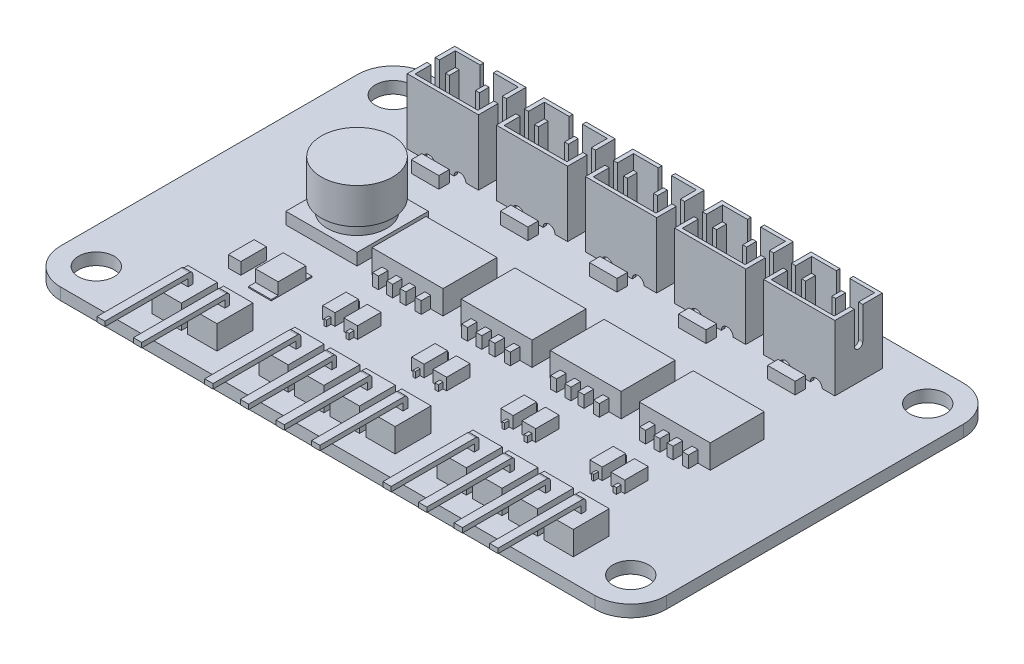
SolidWorks part; units mm, degrees
ref_plane "前视基准面" through (0, 0, 0) normal (0, 0, 1) x (1, 0, 0)
ref_plane "上视基准面" through (0, 0, 0) normal (0, 1, 0) x (1, 0, 0)
ref_plane "右视基准面" through (0, 0, 0) normal (1, 0, 0) x (0, 0, -1)
sketch "草图1" plane through (0, 0, 0) normal (0, 1, 0) x (1, 0, 0)
  line L1 (-22.5, 15.5) -> (22.5, 15.5)
  line L2 (-25.5, 12.5) -> (-25.5, -12.5)
  line L3 (-22.5, -15.5) -> (22.5, -15.5)
  line L4 (25.5, 12.5) -> (25.5, -12.5)
  line L5 (-25.5, 15.5) -> (25.5, -15.5) construction
  line L6 (-25.5, -15.5) -> (25.5, 15.5) construction
  arc A0 (22.5, 15.5) -> (25.5, 12.5) centre (22.5, 12.5) cw
  arc A1 (22.5, -15.5) -> (25.5, -12.5) centre (22.5, -12.5) ccw
  arc A2 (-25.5, -12.5) -> (-22.5, -15.5) centre (-22.5, -12.5) ccw
  arc A3 (-22.5, 15.5) -> (-25.5, 12.5) centre (-22.5, 12.5) ccw
  point P0 (0, 0)
  dimension "D3" = 3
  dimension "D1" = 51
  dimension "D2" = 31
extrude "凸台-拉伸1" add sketch "草图1" along normal blind 1
sketch "草图2" plane through (0, 1, 0) normal (0, 1, 0) x (1, 0, 0)
  line L1 (-22.5, 12.5) -> (22.5, 12.5)
  line L2 (-22.5, 12.5) -> (-22.5, -12.5)
  line L3 (-22.5, -12.5) -> (22.5, -12.5)
  line L4 (22.5, 12.5) -> (22.5, -12.5)
  line L5 (-22.5, 12.5) -> (22.5, -12.5) construction
  line L6 (-22.5, -12.5) -> (22.5, 12.5) construction
  circle A0 centre (-22.5, 12.5) radius 1.5
  point P0 (0, 0)
  dimension "D3" = 3
  dimension "D1" = 45
  dimension "D2" = 25
extrude "切除-拉伸1" cut sketch "草图2" against normal blind 1.5 contours L2 A0 L1 | L1 A0 L2 region at (-22.7122, 1, -12.7122) region at (-21.8634, 1, -11.8634)
mirror "镜向1" about plane through (0, 0, 0) normal (0, 0, 1) of "切除-拉伸1"
mirror "镜向2" about plane through (0, 0, 0) normal (1, 0, 0) of "镜向1"
sketch "草图3" plane through (0, 1, 0) normal (0, 1, 0) x (1, 0, 0)
  line L1 (-17.9678, 13.1472) -> (-11.9678, 13.1472)
  line L2 (-17.9678, 13.1472) -> (-17.9678, 9.1472)
  line L3 (-17.9678, 9.1472) -> (-11.9678, 9.1472)
  line L4 (-11.9678, 13.1472) -> (-11.9678, 9.1472)
  line L5 (-17.9678, 13.1472) -> (-11.9678, 9.1472) construction
  line L6 (-17.9678, 9.1472) -> (-11.9678, 13.1472) construction
  point P4 (-14.9678, 11.1472)
  dimension "D1" = 6
  dimension "D2" = 4
extrude "凸台-拉伸2" add sketch "草图3" along normal blind 5.5
sketch "草图4" plane through (0, 6.5, 0) normal (0, 1, 0) x (1, 0, 0)
  line L1 (-17.6136, 12.8433) -> (-12.3219, 12.8433)
  line L2 (-17.6136, 12.8433) -> (-17.6136, 9.4512)
  line L3 (-17.6136, 9.4512) -> (-12.3219, 9.4512)
  line L4 (-12.3219, 12.8433) -> (-12.3219, 9.4512)
  line L5 (-17.6136, 12.8433) -> (-12.3219, 9.4512) construction
  line L6 (-17.6136, 9.4512) -> (-12.3219, 12.8433) construction
  point P0 (-14.9678, 11.1472)
extrude "切除-拉伸2" cut sketch "草图4" against normal blind 5.5
sketch "草图5" plane through (0, 1, 0) normal (0, 1, 0) x (1, 0, 0)
  line L0 (-14.9678, 12.8433) -> (-14.9678, 9.4512) construction
  line L1 (-12.3219, 12.8433) -> (-17.6136, 12.8433) construction
  line L2 (-17.6136, 9.4512) -> (-12.3219, 9.4512) construction
  line L3 (-13.5358, 10.7921) -> (-13.867, 10.7921)
  line L4 (-16.3997, 11.6123) -> (-16.0685, 11.6123)
  line L5 (-16.3997, 11.6123) -> (-16.3997, 10.7921)
  line L6 (-16.3997, 10.7921) -> (-16.0685, 10.7921)
  line L7 (-16.0685, 11.6123) -> (-16.0685, 10.7921)
  line L8 (-16.3997, 11.6123) -> (-16.0685, 10.7921) construction
  line L9 (-16.3997, 10.7921) -> (-16.0685, 11.6123) construction
  line L10 (-13.867, 11.6123) -> (-13.867, 10.7921)
  line L11 (-13.5358, 11.6123) -> (-13.5358, 10.7921)
  line L12 (-13.5358, 11.6123) -> (-13.867, 11.6123)
  point P10 (-16.2341, 11.2022)
extrude "凸台-拉伸3" add sketch "草图5" along normal blind 5.5
sketch "草图6" plane through (0, 0, -12.8433) normal (0, 0, 1) x (1, 0, 0)
  line L0 (-14.9678, 9.3795) -> (-14.9678, 3.6205) construction
  line L1 (-11.9678, 6.5) -> (-17.9678, 6.5) construction
  line L2 (-14.4041, 9.3795) -> (-14.4041, 3.6205)
  line L3 (-15.5314, 9.3795) -> (-15.5314, 3.6205)
  line L4 (-14.4041, 6.5) -> (-15.5314, 6.5)
  arc A0 (-14.4041, 9.3795) -> (-15.5314, 9.3795) centre (-14.9678, 9.3795) ccw
  arc A1 (-15.5314, 3.6205) -> (-14.4041, 3.6205) centre (-14.9678, 3.6205) ccw
  point P4 (-14.9678, 6.5)
  line M5 (-12.3219, 6.5) -> (-17.6136, 6.5)
extrude "切除-拉伸6" cut sketch "草图6" against normal blind 1 contours L3 A1 L2 L4 M5 region at (-14.9678, 4.8365, -12.8433)
sketch "草图7" plane through (-11.9678, 0, 0) normal (1, 0, 0) x (0, 0, -1)
  line L0 (11.1472, 9.2199) -> (11.1472, 3.7801) construction
  line L1 (9.1472, 6.5) -> (13.1472, 6.5) construction
  line L2 (11.5011, 9.2199) -> (11.5011, 3.7801)
  line L3 (10.7934, 9.2199) -> (10.7934, 3.7801)
  arc A0 (11.5011, 9.2199) -> (10.7934, 9.2199) centre (11.1472, 9.2199) ccw
  arc A1 (10.7934, 3.7801) -> (11.5011, 3.7801) centre (11.1472, 3.7801) ccw
  point P4 (11.1472, 6.5)
extrude "切除-拉伸7" cut sketch "草图7" against normal blind 1
sketch "草图8" plane through (-17.6136, 0, 0) normal (1, 0, 0) x (0, 0, -1)
  line L0 (11.5011, 3.7801) -> (11.5011, 6.5) construction
  line L1 (10.7934, 6.5) -> (10.7934, 3.7801) construction
  line L2 (11.5011, 3.7801) -> (11.5011, 6.5)
  line L3 (10.7934, 6.5) -> (10.7934, 3.7801)
  line L4 (11.5011, 6.5) -> (10.7934, 6.5)
  arc A0 (10.7934, 3.7801) -> (11.5011, 3.7801) centre (11.1472, 3.7801) ccw construction
  arc A1 (10.7934, 3.7801) -> (11.5011, 3.7801) centre (11.1472, 3.7801) ccw
extrude "切除-拉伸8" cut sketch "草图8" against normal blind 1
pattern_linear "阵列(线性)1" count 5 spacing 7.5 along (1, 0, 0) of "凸台-拉伸2"
pattern_linear "阵列(线性)2" count 5 spacing 7.5 along (1, 0, 0) of "切除-拉伸2"
pattern_linear "阵列(线性)3" count 5 spacing 7.5 along (1, 0, 0) of "凸台-拉伸3"
pattern_linear "阵列(线性)4" count 5 spacing 7.5 along (1, 0, 0) of "切除-拉伸7"
pattern_linear "阵列(线性)5" count 5 spacing 7.5 along (1, 0, 0) of "切除-拉伸6"
pattern_linear "阵列(线性)6" count 5 spacing 7.5 along (1, 0, 0) of "切除-拉伸8"
sketch "草图9" plane through (0, 1, 0) normal (0, 1, 0) x (1, 0, 0)
  line L1 (-17.5454, 4.5054) -> (-11.5454, 4.5054)
  line L2 (-17.5454, 4.5054) -> (-17.5454, -1.4946)
  line L3 (-17.5454, -1.4946) -> (-11.5454, -1.4946)
  line L4 (-11.5454, 4.5054) -> (-11.5454, -1.4946)
  line L5 (-17.5454, 4.5054) -> (-11.5454, -1.4946) construction
  line L6 (-17.5454, -1.4946) -> (-11.5454, 4.5054) construction
  point P4 (-14.5454, 1.5054)
  dimension "D1" = 6
  dimension "D2" = 6
extrude "凸台-拉伸4" add sketch "草图9" along normal blind 1
sketch "草图11" plane through (0, 2, 0) normal (0, 1, 0) x (1, 0, 0)
  circle A0 centre (-14.5424, 1.4949) radius 2.5
  point P2 (-14.2861, 1.5685)
  point P3 (0, 0)
  point P4 (0, 0)
  point P5 (0, 0)
  point P6 (0, 0)
  point P7 (-14.5424, 1.4949)
  dimension "D1" = 5
extrude "凸台-拉伸5" add sketch "草图11" along normal blind 1
sketch "草图12" plane through (0, 3, 0) normal (0, 1, 0) x (1, 0, 0)
  circle A0 centre (-14.5424, 1.4949) radius 3
  dimension "D1" = 6
extrude "凸台-拉伸6" add sketch "草图12" along normal blind 3
sketch "草图13" plane through (0, 1, 0) normal (0, 1, 0) x (1, 0, 0)
  line L1 (-16.0248, 8.431) -> (-13.7085, 8.431)
  line L2 (-16.0248, 8.431) -> (-16.0248, 7.5461)
  line L3 (-16.0248, 7.5461) -> (-13.7085, 7.5461)
  line L4 (-13.7085, 8.431) -> (-13.7085, 7.5461)
  line L5 (-16.0248, 8.431) -> (-13.7085, 7.5461) construction
  line L6 (-16.0248, 7.5461) -> (-13.7085, 8.431) construction
  point P4 (-14.8667, 7.9885)
extrude "凸台-拉伸7" add sketch "草图13" along normal blind 1
pattern_linear "阵列(线性)7" count 5 spacing 7.5 along (1, 0, 0) of "凸台-拉伸7"
sketch "草图14" plane through (0, 1, 0) normal (0, 1, 0) x (1, 0, 0)
  line L1 (-10.2665, 3.0233) -> (-4.2896, 3.0233)
  line L2 (-10.2665, 3.0233) -> (-10.2665, -1.5191)
  line L3 (-10.2665, -1.5191) -> (-4.2896, -1.5191)
  line L4 (-4.2896, 3.0233) -> (-4.2896, -1.5191)
  line L5 (-10.2665, 3.0233) -> (-4.2896, -1.5191) construction
  line L6 (-10.2665, -1.5191) -> (-4.2896, 3.0233) construction
  point P4 (-7.278, 0.7521)
extrude "凸台-拉伸8" add sketch "草图14" along normal blind 2
sketch "草图15" plane through (0, 1, 0) normal (0, 1, 0) x (1, 0, 0)
  line L0 (-4.2896, 3.0233) -> (-10.2665, 3.0233) construction
  line L1 (-9.4235, 3.8286) -> (-8.9235, 3.8286)
  line L2 (-9.4235, 3.8286) -> (-9.4235, 3.0233)
  line L3 (-9.4235, 3.0233) -> (-8.9235, 3.0233)
  line L4 (-8.9235, 3.8286) -> (-8.9235, 3.0233)
  line L5 (-9.4235, 3.8286) -> (-8.9235, 3.0233) construction
  line L6 (-9.4235, 3.0233) -> (-8.9235, 3.8286) construction
  line L7 (-4.2896, 3.0233) -> (-10.2665, 3.0233) construction
  line L8 (-8.2218, 3.8286) -> (-7.7218, 3.8286)
  line L9 (-8.2218, 3.8286) -> (-8.2218, 3.0233)
  line L10 (-8.2218, 3.0233) -> (-7.7218, 3.0233)
  line L11 (-7.7218, 3.8286) -> (-7.7218, 3.0233)
  line L12 (-8.2218, 3.8286) -> (-7.7218, 3.0233) construction
  line L13 (-8.2218, 3.0233) -> (-7.7218, 3.8286) construction
  line L14 (-10.2665, 0.7521) -> (-4.2896, 0.7521) construction
  line L15 (-7.1123, 3.8286) -> (-6.6123, 3.8286)
  line L16 (-7.1123, 3.8286) -> (-7.1123, 3.0233)
  line L17 (-7.1123, 3.0233) -> (-6.6123, 3.0233)
  line L18 (-6.6123, 3.8286) -> (-6.6123, 3.0233)
  line L19 (-7.1123, 3.8286) -> (-6.6123, 3.0233) construction
  line L20 (-7.1123, 3.0233) -> (-6.6123, 3.8286) construction
  line L21 (-5.822, 3.8286) -> (-5.322, 3.8286)
  line L22 (-5.822, 3.8286) -> (-5.822, 3.0233)
  line L23 (-5.822, 3.0233) -> (-5.322, 3.0233)
  line L24 (-5.322, 3.8286) -> (-5.322, 3.0233)
  line L25 (-5.822, 3.8286) -> (-5.322, 3.0233) construction
  line L26 (-5.822, 3.0233) -> (-5.322, 3.8286) construction
  line L27 (-10.2665, 3.0233) -> (-10.2665, -1.5191) construction
  line L28 (-4.2896, -1.5191) -> (-4.2896, 3.0233) construction
  line L29 (-5.822, -1.5191) -> (-5.322, -2.3244) construction
  line L30 (-5.822, -2.3244) -> (-5.322, -1.5191) construction
  line L31 (-7.1123, -1.5191) -> (-6.6123, -2.3244) construction
  line L32 (-7.1123, -2.3244) -> (-6.6123, -1.5191) construction
  line L33 (-8.2218, -1.5191) -> (-7.7218, -2.3244) construction
  line L34 (-8.2218, -2.3244) -> (-7.7218, -1.5191) construction
  line L35 (-9.4235, -1.5191) -> (-8.9235, -2.3244) construction
  line L36 (-9.4235, -2.3244) -> (-8.9235, -1.5191) construction
  line L37 (-5.322, -2.3244) -> (-5.322, -1.5191)
  line L38 (-5.822, -1.5191) -> (-5.322, -1.5191)
  line L39 (-5.822, -2.3244) -> (-5.822, -1.5191)
  line L40 (-5.822, -2.3244) -> (-5.322, -2.3244)
  line L41 (-6.6123, -2.3244) -> (-6.6123, -1.5191)
  line L42 (-7.1123, -1.5191) -> (-6.6123, -1.5191)
  line L43 (-7.1123, -2.3244) -> (-7.1123, -1.5191)
  line L44 (-7.1123, -2.3244) -> (-6.6123, -2.3244)
  line L45 (-7.7218, -2.3244) -> (-7.7218, -1.5191)
  line L46 (-8.2218, -1.5191) -> (-7.7218, -1.5191)
  line L47 (-8.2218, -2.3244) -> (-8.2218, -1.5191)
  line L48 (-8.2218, -2.3244) -> (-7.7218, -2.3244)
  line L49 (-8.9235, -2.3244) -> (-8.9235, -1.5191)
  line L50 (-9.4235, -1.5191) -> (-8.9235, -1.5191)
  line L51 (-9.4235, -2.3244) -> (-9.4235, -1.5191)
  line L52 (-9.4235, -2.3244) -> (-8.9235, -2.3244)
  point P4 (-9.1735, 3.4259)
  point P11 (-7.9718, 3.4259)
  point P18 (-6.8623, 3.4259)
  point P23 (-5.572, 3.4259)
  point P46 (-5.572, -1.9218)
  point P47 (-6.8623, -1.9218)
  point P48 (-7.9718, -1.9218)
  point P49 (-9.1735, -1.9218)
  dimension "D1" = 0.5
  dimension "D2" = 0.5
  dimension "D3" = 0.5
  dimension "D4" = 0.5
extrude "凸台-拉伸9" add sketch "草图15" along normal blind 1
pattern_linear "阵列(线性)8" count 4 spacing 7.5 along (1, 0, 0) of "凸台-拉伸9"
pattern_linear "阵列(线性)9" count 4 spacing 7.5 along (1, 0, 0) of "凸台-拉伸8"
sketch "草图16" plane through (0, 1, 0) normal (0, 1, 0) x (1, 0, 0)
  line L1 (-9.1178, -4.8537) -> (-8.0747, -4.8537)
  line L2 (-9.1178, -4.8537) -> (-9.1178, -6.828)
  line L3 (-9.1178, -6.828) -> (-8.0747, -6.828)
  line L4 (-8.0747, -4.8537) -> (-8.0747, -6.828)
  line L5 (-9.1178, -4.8537) -> (-8.0747, -6.828) construction
  line L6 (-9.1178, -6.828) -> (-8.0747, -4.8537) construction
  line L7 (-7.3297, -4.8537) -> (-6.1749, -4.8537)
  line L8 (-7.3297, -4.8537) -> (-7.3297, -6.828)
  line L9 (-7.3297, -6.828) -> (-6.1749, -6.828)
  line L10 (-6.1749, -4.8537) -> (-6.1749, -6.828)
  line L11 (-7.3297, -4.8537) -> (-6.1749, -6.828) construction
  line L12 (-7.3297, -6.828) -> (-6.1749, -4.8537) construction
  point P4 (-8.5963, -5.8408)
  point P9 (-6.7523, -5.8408)
extrude "凸台-拉伸10" add sketch "草图16" along normal blind 1
sketch "草图17" plane through (0, 1, 0) normal (0, 1, 0) x (1, 0, 0)
  line L0 (-8.0747, -4.8537) -> (-9.1178, -4.8537) construction
  line L1 (-8.7404, -4.438) -> (-8.4045, -4.438)
  line L2 (-8.7404, -4.438) -> (-8.7404, -4.8537)
  line L3 (-8.7404, -4.8537) -> (-8.4045, -4.8537)
  line L4 (-8.4045, -4.438) -> (-8.4045, -4.8537)
  line L5 (-8.7404, -4.438) -> (-8.4045, -4.8537) construction
  line L6 (-8.7404, -4.8537) -> (-8.4045, -4.438) construction
  line L7 (-6.1749, -4.8537) -> (-7.3297, -4.8537) construction
  line L8 (-6.9018, -4.438) -> (-6.619, -4.438)
  line L9 (-6.9018, -4.438) -> (-6.9018, -4.8537)
  line L10 (-6.9018, -4.8537) -> (-6.619, -4.8537)
  line L11 (-6.619, -4.438) -> (-6.619, -4.8537)
  line L12 (-6.9018, -4.438) -> (-6.619, -4.8537) construction
  line L13 (-6.9018, -4.8537) -> (-6.619, -4.438) construction
  line L14 (-9.1178, -6.828) -> (-8.0747, -6.828) construction
  line L15 (-8.5963, -6.828) -> (-8.4045, -6.828)
  line L16 (-8.5963, -6.828) -> (-8.5963, -7.2313)
  line L17 (-8.5963, -7.2313) -> (-8.4045, -7.2313)
  line L18 (-8.4045, -6.828) -> (-8.4045, -7.2313)
  line L19 (-8.5963, -6.828) -> (-8.4045, -7.2313) construction
  line L20 (-8.5963, -7.2313) -> (-8.4045, -6.828) construction
  line L21 (-7.3297, -6.828) -> (-6.1749, -6.828) construction
  line L22 (-6.7523, -6.828) -> (-6.4776, -6.828)
  line L23 (-6.7523, -6.828) -> (-6.7523, -7.2313)
  line L24 (-6.7523, -7.2313) -> (-6.4776, -7.2313)
  line L25 (-6.4776, -6.828) -> (-6.4776, -7.2313)
  line L26 (-6.7523, -6.828) -> (-6.4776, -7.2313) construction
  line L27 (-6.7523, -7.2313) -> (-6.4776, -6.828) construction
  point P4 (-8.5725, -4.6459)
  point P11 (-6.7604, -4.6459)
  point P18 (-8.5004, -7.0296)
  point P25 (-6.6149, -7.0296)
extrude "凸台-拉伸11" add sketch "草图17" along normal blind 0.5
pattern_linear "阵列(线性)10" count 4 spacing 7.5 along (1, 0, 0) of "凸台-拉伸11"
pattern_linear "阵列(线性)11" count 4 spacing 7.5 along (1, 0, 0) of "凸台-拉伸10"
sketch "草图18" plane through (0, 1, 0) normal (0, 1, 0) x (1, 0, 0)
  line L1 (-14.5341, -4.2207) -> (-12.6247, -4.2207)
  line L2 (-14.5341, -4.2207) -> (-14.5341, -7.6506)
  line L3 (-14.5341, -7.6506) -> (-12.6247, -7.6506)
  line L4 (-12.6247, -4.2207) -> (-12.6247, -7.6506)
  line L5 (-14.5341, -4.2207) -> (-12.6247, -7.6506) construction
  line L6 (-14.5341, -7.6506) -> (-12.6247, -4.2207) construction
  point P4 (-13.5794, -5.9356)
extrude "凸台-拉伸12" add sketch "草图18" along normal blind 0.1
sketch "草图19" plane through (0, 1.1, 0) normal (0, 1, 0) x (1, 0, 0)
  line L0 (-14.5341, -4.2207) -> (-14.5341, -7.6506) construction
  line L1 (-14.5341, -4.7332) -> (-12.6247, -4.7332)
  line L2 (-14.5341, -4.7332) -> (-14.5341, -7.0658)
  line L3 (-14.5341, -7.0658) -> (-12.6247, -7.0658)
  line L4 (-12.6247, -4.7332) -> (-12.6247, -7.0658)
  line L5 (-14.5341, -4.7332) -> (-12.6247, -7.0658) construction
  line L6 (-14.5341, -7.0658) -> (-12.6247, -4.7332) construction
  line L7 (-12.6247, -7.6506) -> (-12.6247, -4.2207) construction
  point P4 (-13.5794, -5.8995)
extrude "凸台-拉伸13" add sketch "草图19" along normal blind 1
sketch "草图20" plane through (0, 1, 0) normal (0, 1, 0) x (1, 0, 0)
  line L1 (-16.8123, -4.901) -> (-15.7719, -4.901)
  line L2 (-16.8123, -4.901) -> (-16.8123, -7.0658)
  line L3 (-16.8123, -7.0658) -> (-15.7719, -7.0658)
  line L4 (-15.7719, -4.901) -> (-15.7719, -7.0658)
  line L5 (-16.8123, -4.901) -> (-15.7719, -7.0658) construction
  line L6 (-16.8123, -7.0658) -> (-15.7719, -4.901) construction
  point P4 (-16.2921, -5.9834)
extrude "凸台-拉伸14" add sketch "草图20" along normal blind 1
sketch "草图21" plane through (0, 1, 0) normal (0, 1, 0) x (1, 0, 0)
  line L1 (-16.716, -10.5687) -> (-14.2453, -10.5687)
  line L2 (-16.716, -10.5687) -> (-16.716, -13.5961)
  line L3 (-16.716, -13.5961) -> (-14.2453, -13.5961)
  line L4 (-14.2453, -10.5687) -> (-14.2453, -13.5961)
  line L5 (-16.716, -10.5687) -> (-14.2453, -13.5961) construction
  line L6 (-16.716, -13.5961) -> (-14.2453, -10.5687) construction
  point P4 (-15.4806, -12.0824)
extrude "凸台-拉伸15" add sketch "草图21" along normal blind 2
sketch "草图22" plane through (0, 3, 0) normal (0, 1, 0) x (1, 0, 0)
  line L0 (-14.2453, -13.5961) -> (-14.2453, -10.5687) construction
  line L1 (-15.816, -11.7283) -> (-15.1453, -11.7283)
  line L2 (-15.816, -11.7283) -> (-15.816, -12.1283)
  line L3 (-15.816, -12.1283) -> (-15.1453, -12.1283)
  line L4 (-15.1453, -11.7283) -> (-15.1453, -12.1283)
  line L5 (-15.816, -11.7283) -> (-15.1453, -12.1283) construction
  line L6 (-15.816, -12.1283) -> (-15.1453, -11.7283) construction
  line L7 (-16.716, -10.5687) -> (-16.716, -13.5961) construction
  point P4 (-15.4806, -11.9283)
  dimension "D1" = 0.9
  dimension "D2" = 0.9
  dimension "D3" = 0.4
extrude "凸台-拉伸16" add sketch "草图22" along normal blind 1
sketch "草图23" plane through (0, 0, 12.1283) normal (0, 0, 1) x (1, 0, 0)
  line L0 (-15.1453, 4) -> (-15.1453, 3) construction
  line L1 (-15.816, 4) -> (-15.1453, 4)
  line L2 (-15.816, 4) -> (-15.816, 3.6)
  line L3 (-15.816, 3.6) -> (-15.1453, 3.6)
  line L4 (-15.1453, 4) -> (-15.1453, 3.6)
  line L5 (-15.816, 4) -> (-15.1453, 3.6) construction
  line L6 (-15.816, 3.6) -> (-15.1453, 4) construction
  point P4 (-15.4806, 3.8)
  dimension "D1" = 0.4
extrude "凸台-拉伸17" add sketch "草图23" along normal blind 7
fillet "圆角1" radius 0.3 1 edges at (-15.4806, 4, 11.7283)
pattern_linear "阵列(线性)12" count 12 spacing 3 along (1, 0, 0) skipping (2, 0), (7, 0) of "凸台-拉伸15"
sketch "草图24" plane through (0, 0, -9.1472) normal (0, 0, 1) x (1, 0, 0)
  line L0 (-17.9678, 1) -> (-11.9678, 1) construction
  line L1 (-16.5178, 1) -> (-13.0312, 1)
  line L2 (-16.5178, 1) -> (-16.7272, 1)
  circle A0 centre (-13.5312, 1) radius 0.5
  circle A1 centre (-16.1286, 1) radius 0.5
  line M1 (-17.9678, 1) -> (-11.9678, 1)
  dimension "D1" = 1
  dimension "D2" = 1
extrude "切除-拉伸9" cut sketch "草图24" against normal blind 1 contours L1 A0 | A1 L2 M1 region at (-16.1286, 1.2122, -9.1472) region at (-13.5312, 1.2122, -9.1472)
pattern_linear "阵列(线性)16" count 5 spacing 7.5 along (1, 0, 0) of "切除-拉伸9"
ref_plane "基准面1" through (-12.0453, 0, 0) normal (1, 0, 0) x (0, 0, -1)
sketch "草图25" plane through (-12.0453, 0, 0) normal (1, 0, 0) x (0, 0, -1)
  line L6 (-11.7283, 3) -> (-11.7283, 3.7)
  line L7 (-12.0283, 4) -> (-19.1283, 4)
  line L8 (-19.1283, 4) -> (-19.1283, 3.6)
  line L9 (-19.1283, 3.6) -> (-12.1283, 3.6)
  line L10 (-12.1283, 3.6) -> (-12.1283, 3)
  line L11 (-12.1283, 3) -> (-11.7283, 3)
  line L12 (-11.7283, 3) -> (-11.7283, 3.7)
  line L13 (-12.0283, 4) -> (-19.1283, 4)
  line L14 (-19.1283, 4) -> (-19.1283, 3.6)
  line L15 (-19.1283, 3.6) -> (-12.1283, 3.6)
  line L16 (-12.1283, 3.6) -> (-12.1283, 3)
  line L17 (-12.1283, 3) -> (-11.7283, 3)
  arc A1 (-11.7283, 3.7) -> (-12.0283, 4) centre (-12.0283, 3.7) ccw
  arc A2 (-11.7283, 3.7) -> (-12.0283, 4) centre (-12.0283, 3.7) ccw
  dimension "D1" = 0
extrude "凸台-拉伸18" add sketch "草图25" against normal blind 0.7
pattern_linear "阵列(线性)21" count 12 spacing 3 along (1, 0, 0) skipping (1, 0), (6, 0), (11, 0) of "凸台-拉伸18"
